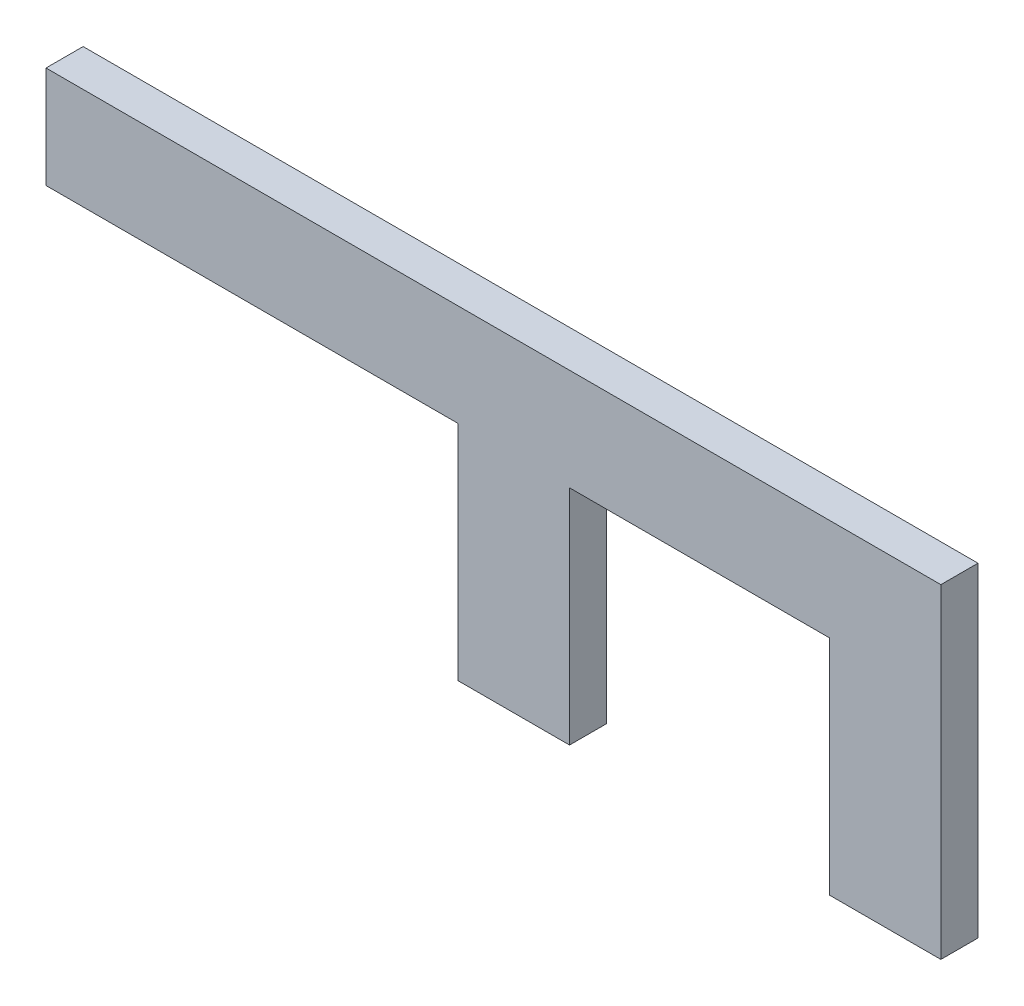
SolidWorks part; units mm, degrees
ref_plane "Front Plane" through (0, 0, 0) normal (0, 0, 1) x (1, 0, 0)
ref_plane "Top Plane" through (0, 0, 0) normal (0, 1, 0) x (1, 0, 0)
ref_plane "Right Plane" through (0, 0, 0) normal (1, 0, 0) x (0, 0, -1)
sketch "Sketch1" plane through (0, 0, 0) normal (0, 0, 1) x (1, 0, 0)
  line L1 (0, 0) -> (240.9905, 0)
  line L2 (0, 0) -> (0, -27.4161)
  line L3 (0, -27.4161) -> (240.9905, -27.4161)
  line L4 (240.9905, 0) -> (240.9905, -27.4161)
extrude "Boss-Extrude1" add sketch "Sketch1" along normal blind 10
sketch "Sketch2" plane through (0, -27.4161, 0) normal (0, -1, 0) x (-1, 0, 0)
  line L0 (0, 0) -> (-240.9905, 0) construction
  line L1 (-240.9905, -10) -> (-210.9905, -10)
  line L2 (-240.9905, -10) -> (-240.9905, 0)
  line L3 (-240.9905, 0) -> (-210.9905, 0)
  line L4 (-210.9905, -10) -> (-210.9905, 0)
  dimension "D1" = 30
extrude "Boss-Extrude2" add sketch "Sketch2" along normal blind 60
sketch "Sketch3" plane through (0, -27.4161, 0) normal (0, -1, 0) x (-1, 0, 0)
  line L0 (0, -10) -> (-210.9905, -10) construction
  line L1 (-140.9905, -10) -> (-110.9905, -10)
  line L2 (-140.9905, -10) -> (-140.9905, 0)
  line L3 (-140.9905, 0) -> (-110.9905, 0)
  line L4 (-110.9905, -10) -> (-110.9905, 0)
  line L5 (0, 0) -> (-210.9905, 0) construction
  line L6 (-210.9905, -10) -> (-210.9905, 0) construction
  dimension "D1" = 30
  dimension "D2" = 70
extrude "Boss-Extrude3" add sketch "Sketch3" along normal blind 60
